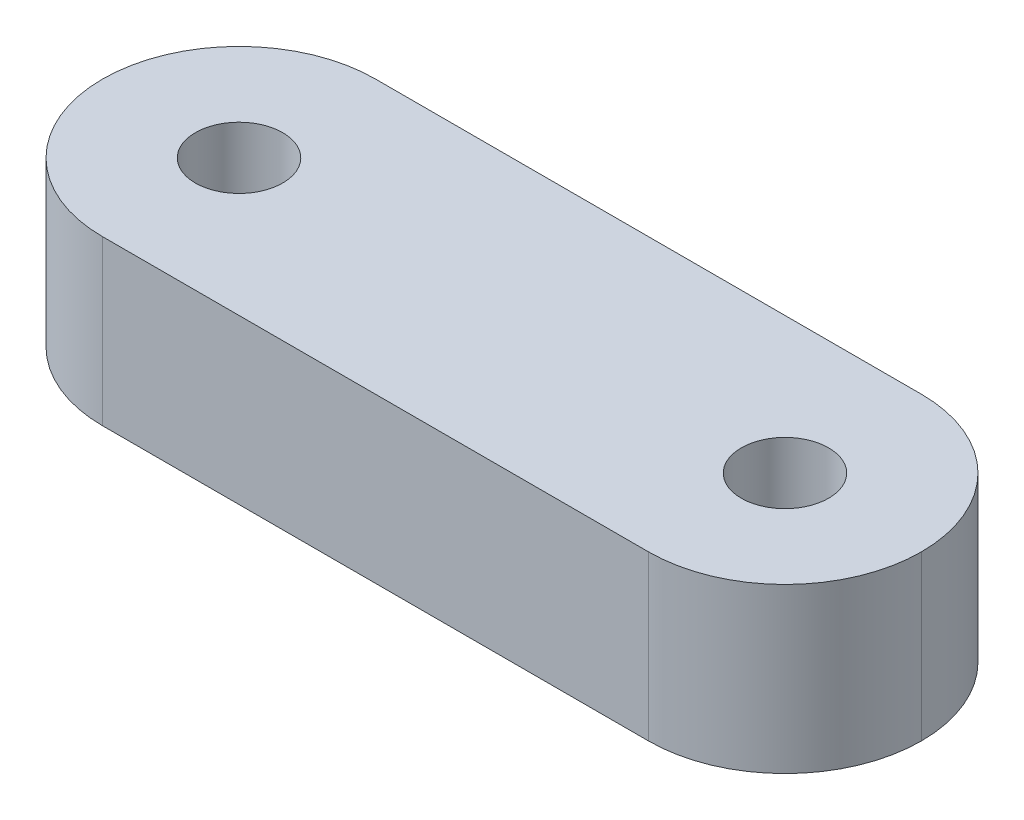
SolidWorks part; units mm, degrees
material "Maple"
ref_plane "Front Plane" through (0, 0, 0) normal (0, 0, 1) x (1, 0, 0)
ref_plane "Top Plane" through (0, 0, 0) normal (0, 1, 0) x (1, 0, 0)
ref_plane "Right Plane" through (0, 0, 0) normal (1, 0, 0) x (0, 0, -1)
sketch "Sketch2" plane through (0, 0, 0) normal (0, 1, 0) x (1, 0, 0)
  line L1 (-15, 5) -> (15, 5)
  line L2 (-15, 5) -> (-15, -5)
  line L3 (-15, -5) -> (15, -5)
  line L4 (15, 5) -> (15, -5)
  line L5 (-15, 5) -> (15, -5) construction
  line L6 (-15, -5) -> (15, 5) construction
  point P0 (0, 0)
  dimension "D1" = 30
  dimension "D2" = 10
extrude "Boss-Extrude1" add sketch "Sketch2" along normal blind 6
hole_wizard "M3 Clearance Hole1" positions "Sketch4" profile "Sketch3" hole size "M3" standard "ANSI Metric" end condition through all
sketch "Sketch4" plane through (0, 6, 0) normal (0, 1, 0) x (1, 0, 0)
  line L0 (-10, 0) -> (10, 0) construction
  point P0 (-10, 0)
  point P2 (10, 0)
  dimension "D1" = 20
sketch "Sketch3" plane through (-10, 6, 0) normal (1, 0, 0) x (0, 0, 1)
  line L0 (0, 0) -> (0, 6)
  line L1 (0, 6) -> (1.6, 6)
  line L2 (1.6, 6) -> (1.6, 0)
  line L5 (1.6, 0) -> (0, 0)
  line L11 (0, -6.35) -> (0, 107.95) construction
  dimension "Thru Hole Dia." = 3.2
  dimension "Thru Hole Depth" = 6
fillet "Fillet1" radius 5 4 edges at (15, 3, -5) (15, 3, 5) (-15, 3, 5) (-15, 3, -5)
